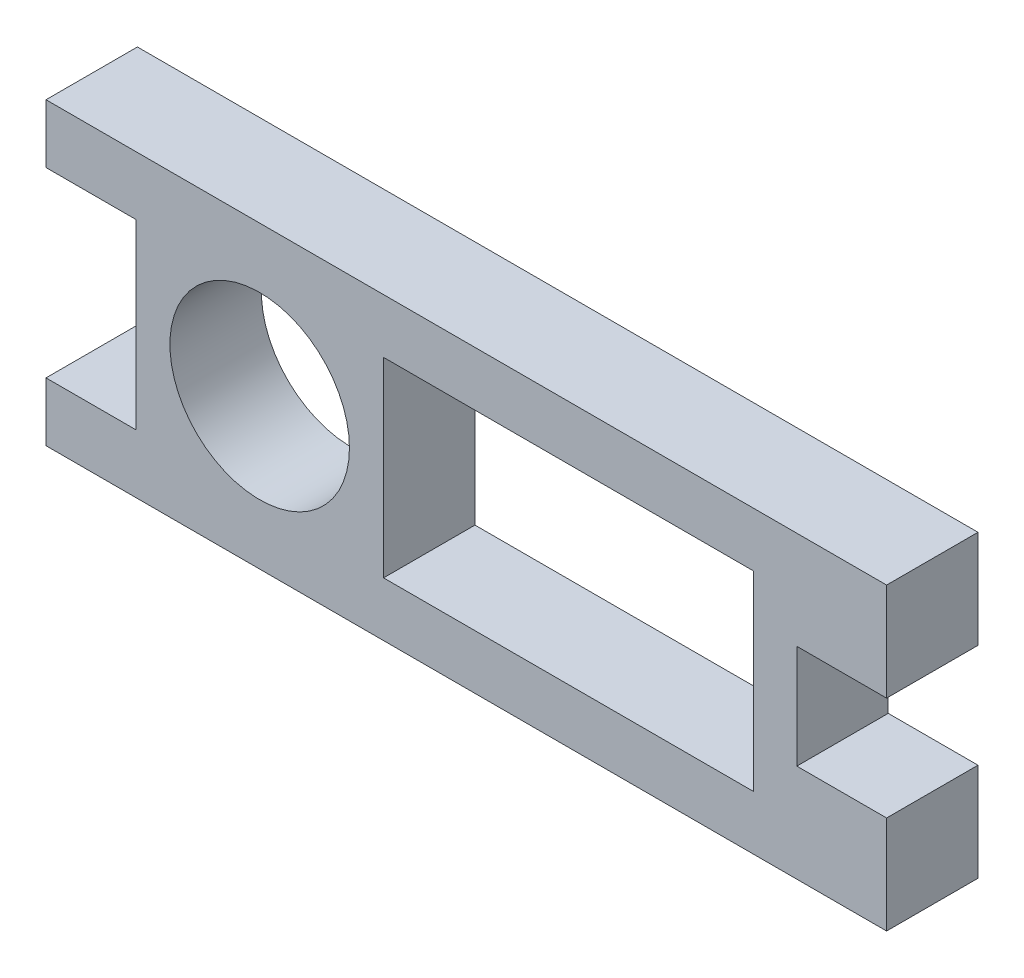
SolidWorks part; units mm, degrees
material "Acrylic (Medium-high impact)"
ref_plane "Front Plane" through (0, 0, 0) normal (0, 0, 1) x (1, 0, 0)
ref_plane "Top Plane" through (0, 0, 0) normal (0, 1, 0) x (1, 0, 0)
ref_plane "Right Plane" through (0, 0, 0) normal (1, 0, 0) x (0, 0, -1)
sketch "Sketch1" plane through (0, 0, 0) normal (0, 0, 1) x (1, 0, 0)
  line L0 (-297.7097, 397.165) -> (49702.2903, 397.165) construction
  line L1 (702.2903, 402.744) -> (702.2903, 391.586)
  line L2 (702.2903, 402.744) -> (696.7903, 402.744)
  line L3 (696.7903, 402.744) -> (696.7903, 406.344)
  line L4 (696.7903, 406.344) -> (748.2903, 406.344)
  line L5 (748.2903, 406.344) -> (748.2903, 400.344)
  line L6 (748.2903, 400.344) -> (742.7903, 400.344)
  line L7 (742.7903, 400.344) -> (742.7903, 393.986)
  line L8 (742.7903, 393.986) -> (748.2903, 393.986)
  line L9 (748.2903, 393.986) -> (748.2903, 387.986)
  line L10 (748.2903, 387.986) -> (696.7903, 387.986)
  line L11 (696.7903, 387.986) -> (696.7903, 391.586)
  line L12 (696.7903, 391.586) -> (702.2903, 391.586)
  line L13 (709.8808, -602.835) -> (709.8808, 49397.165) construction
  line L14 (717.4713, 391.315) -> (740.1403, 391.315)
  line L15 (717.4713, 391.315) -> (717.4713, 403.015)
  line L16 (717.4713, 403.015) -> (740.1403, 403.015)
  line L17 (740.1403, 391.315) -> (740.1403, 403.015)
  circle A0 centre (709.8808, 397.165) radius 5.5
  point P0 (702.2903, 397.165)
  point P19 (717.4713, 397.165)
  dimension "D10" = 11
  dimension "D2" = 3.6
  dimension "D4" = 5.5
  dimension "D5" = 5.5
  dimension "D6" = 6
  dimension "D7" = 6.358
extrude "Boss-Extrude1" add sketch "Sketch1" along normal blind 5.6
